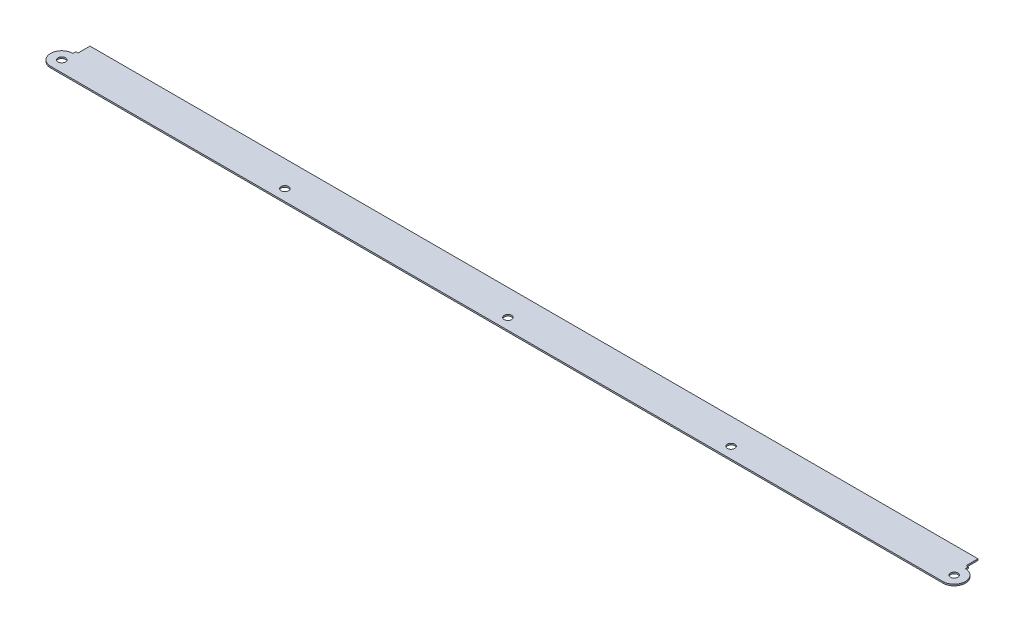
SolidWorks part; units mm, degrees
ref_plane "Front Plane" through (0, 0, 0) normal (0, 0, 1) x (1, 0, 0)
ref_plane "Top Plane" through (0, 0, 0) normal (0, 1, 0) x (1, 0, 0)
ref_plane "Right Plane" through (0, 0, 0) normal (1, 0, 0) x (0, 0, -1)
sketch "Sketch1" plane through (0, 0, 0) normal (0, 1, 0) x (1, 0, 0)
  line L0 (-300, 0) -> (300, 0) construction
  line L1 (-300, 7.5) -> (300, 7.5) construction
  line L2 (-300, 7.5) -> (-300, -7.5) construction
  line L3 (-300, -7.5) -> (300, -7.5)
  line L4 (300, 7.5) -> (300, -7.5) construction
  line L5 (-300, 7.5) -> (300, -7.5) construction
  line L6 (-300, -7.5) -> (300, 7.5) construction
  line L9 (-298.5, 17.5) -> (298.5, 17.5)
  line L12 (-300, 7.5) -> (-300, 9.5)
  line L13 (-300, 9.5) -> (-298.5, 9.5)
  line L14 (-298.5, 9.5) -> (-298.5, 17.5)
  line L15 (300, 7.5) -> (300, 9.5)
  line L16 (300, 9.5) -> (298.5, 9.5)
  line L17 (298.5, 9.5) -> (298.5, 17.5)
  line L19 (0, 0) -> (0, 17.5) construction
  circle A0 centre (0, 0) radius 2.5
  arc A2 (-300, 7.5) -> (-300, -7.5) centre (-300, 0) ccw
  arc A3 (300, 7.5) -> (300, -7.5) centre (300, 0) cw
  circle A4 centre (150, 0) radius 2.5
  circle A5 centre (-150, 0) radius 2.5
  circle A6 centre (-300, 0) radius 2.5
  circle A7 centre (300, 0) radius 2.5
  point P9 (-299.25, 9.5)
  dimension "D1" = 5
  dimension "D2" = 600
  dimension "D3" = 2
  dimension "D4" = 15
  dimension "D5" = 10
  dimension "D6" = 3
  dimension "D7" = 3
  dimension "D8" = 3
extrude "Boss-Extrude1" add sketch "Sketch1" along normal blind 1
